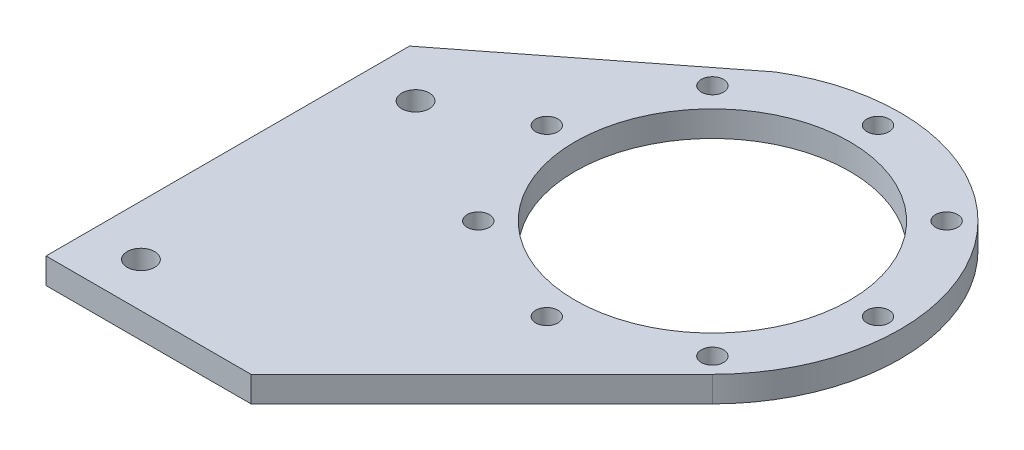
SolidWorks part; units mm, degrees
ref_plane "Front Plane" through (0, 0, 0) normal (0, 0, 1) x (1, 0, 0)
ref_plane "Top Plane" through (0, 0, 0) normal (0, 1, 0) x (1, 0, 0)
ref_plane "Right Plane" through (0, 0, 0) normal (1, 0, 0) x (0, 0, -1)
sketch "Sketch2" plane through (0, 0, 0) normal (0, 1, 0) x (1, 0, 0)
  line L0 (50.7609, 129.6827) -> (50.7609, 0) construction
  line L1 (0, 0) -> (50.7609, 0)
  line L2 (0, 0) -> (0, 90)
  line L6 (107.8805, 57.1195) -> (50.7609, 0)
  line L8 (0, 129.6827) -> (0, 90) construction
  line L9 (0, 90) -> (75, 90) construction
  line L10 (0, 90) -> (50.7609, 129.6827)
  arc A1 (50.7609, 129.6827) -> (107.8805, 57.1195) centre (75, 90) cw
  dimension "D1" = 90
  dimension "46.5" = 46.5
  dimension "D2" = 75
  dimension "D5" = 45
base flange "Base-Flange1" sketch "Sketch2" thickness 6.35 reverse thickness direction no parameters "D1"=0.7366
sketch "Sketch8" plane through (0, 0, 0) normal (0, 1, 0) x (1, 0, 0)
  line L1 (0, 90) -> (0, 0) construction
  line L2 (0, 45) -> (79.3207, 45) construction
  line L3 (0, 90) -> (121.5, 90) construction
  line L4 (79.3207, 28.5598) -> (79.3207, 90) construction
  line L5 (50.7609, 0) -> (107.8805, 57.1195) construction
  line L6 (0, 90) -> (0, 0) construction
  circle A1 centre (12.5, 79) radius 3.4
  circle A3 centre (12.5, 11) radius 3.4
  arc A4 (107.8805, 57.1195) -> (50.7609, 129.6827) centre (75, 90) ccw construction
  dimension "D1" = 6.8
  dimension "D3" = 12.5
  dimension "D2" = 11
extrude "Cut-Extrude1" cut sketch "Sketch8" against normal through all normal cut yes
sketch "Sketch9" plane through (0, 0, 0) normal (0, 1, 0) x (1, 0, 0)
  arc A0 (107.8805, 57.1195) -> (50.7609, 129.6827) centre (75, 90) ccw construction
  arc A1 (107.8805, 57.1195) -> (50.7609, 129.6827) centre (75, 90) ccw construction
  circle A2 centre (75, 90) radius 34
  dimension "D1" = 68
extrude "Cut-Extrude2" cut sketch "Sketch9" against normal through all normal cut yes
sketch "Sketch10" plane through (0, 0, 0) normal (0, 1, 0) x (1, 0, 0)
  circle A0 centre (75, 90) radius 41 construction
  circle A1 centre (75, 131) radius 2.75
  circle A2 centre (103.9914, 118.9914) radius 2.75
  circle A3 centre (116, 90) radius 2.75
  circle A4 centre (103.9914, 61.0086) radius 2.75
  circle A5 centre (75, 49) radius 2.75
  circle A6 centre (46.0086, 61.0086) radius 2.75
  circle A7 centre (34, 90) radius 2.75
  circle A8 centre (46.0086, 118.9914) radius 2.75
  point P22 (75, 90)
  dimension "D1" = 82
  dimension "D2" = 5.5
  dimension "D3" = 8
extrude "Cut-Extrude3" cut sketch "Sketch10" against normal through all normal cut yes
sketch "Bend-Lines1" [suppressed] plane through (0, 0, 0) normal (0, 1, 0) x (1, 0, 0)
sketch "Bounding-Box1" [suppressed] plane through (0, 0, 0) normal (0, 1, 0) x (1, 0, 0)
sheet metal parameters "Sheet-Metal1" thickness 6.35 parameters "D1"=0.7366
flat pattern "Flat-Pattern1" [suppressed]
sketch "Bend-Lines2" plane through (0, 0, 0) normal (0, 1, 0) x (1, 0, 0)
sketch3d "Bounding-Box2" [suppressed]
  line L0 (37.25, -37.25, 0) -> (37.25, 37.25, 0) construction
  line L1 (-22.5, -37.25, 0) -> (-22.5, 37.25, 0) construction
  line L2 (37.25, -37.25, 0) -> (-22.5, -37.25, 0) construction
  line L3 (37.25, 37.25, 0) -> (-22.5, 37.25, 0) construction
sheet metal parameters "Sheet-Metal2" thickness 6.35 parameters "D1"=0.7366
flat pattern "Flat-Pattern1"
sketch "Bend-Lines2" plane through (0, 0, 0) normal (0, 1, 0) x (1, 0, 0)
sketch3d "Bounding-Box2" [suppressed]
  line L0 (-106, -39.1795, 0) -> (-7.0705, 59.75, 0) construction
  line L1 (-46.25, -98.9295, 0) -> (52.6795, 0, 0) construction
  line L2 (-106, -39.1795, 0) -> (-46.25, -98.9295, 0) construction
  line L3 (-7.0705, 59.75, 0) -> (52.6795, 0, 0) construction
sheet metal parameters "Sheet-Metal3" thickness 6.35 parameters "D1"=0.7366
flat pattern "Flat-Pattern1"
sketch "Bend-Lines2" plane through (0, 0, 0) normal (0, 1, 0) x (1, 0, 0)
sketch3d "Bounding-Box2" [suppressed]
  line L0 (-107.7298, -46.3484, 0) -> (0.0689, 64.7304, 0) construction
  line L1 (-42.0452, -110.0934, 0) -> (65.7535, 0.9853, 0) construction
  line L2 (-107.7298, -46.3484, 0) -> (-42.0452, -110.0934, 0) construction
  line L3 (0.0689, 64.7304, 0) -> (65.7535, 0.9853, 0) construction
sheet metal parameters "Sheet-Metal4" thickness 6.35 parameters "D1"=0.7366
flat pattern "Flat-Pattern1"
sketch "Bend-Lines2" plane through (0, 0, 0) normal (0, 1, 0) x (1, 0, 0)
sketch3d "Bounding-Box2" [suppressed]
  line L0 (-120, -45, 0) -> (-4.6195, 70.3805, 0) construction
  line L1 (-49.6195, -115.3805, 0) -> (65.7609, 0, 0) construction
  line L2 (-120, -45, 0) -> (-49.6195, -115.3805, 0) construction
  line L3 (-4.6195, 70.3805, 0) -> (65.7609, 0, 0) construction
equation "\"L1L\"=500"
equation "\"L1Thick\"=6.35"
equation "\"Harm-Drive-Outer\"=74.5"
equation "\"L1-Spacing\"=115.65"
equation "\"L-Bracket-HoleToWall\"=12.5"
equation "\"Bracket-Hole-D\"=6.8"
equation "\"D1@Sketch8\"=\"Bracket-Hole-D\""
equation "\"L-Bracket-HoleToSide\"=11"
equation "\"D3@Sketch8\"=\"L-Bracket-HoleToWall\""
equation "\"D2@Sketch8\"=\"L-Bracket-HoleToSide\""
